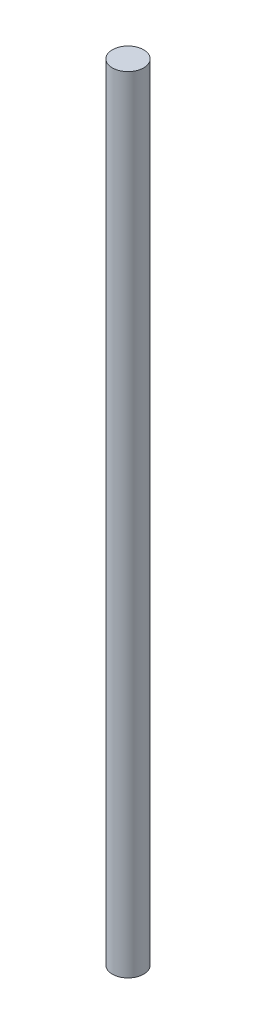
SolidWorks part; units mm, degrees
ref_plane "Plano frontal" through (0, 0, 0) normal (0, 0, 1) x (1, 0, 0)
ref_plane "Plano superior" through (0, 0, 0) normal (0, 1, 0) x (1, 0, 0)
ref_plane "Plano direito" through (0, 0, 0) normal (1, 0, 0) x (0, 0, -1)
sketch "Esboço1" plane through (0, 0, 0) normal (0, 0, 1) x (1, 0, 0)
  line L0 (0, 0) -> (0, 1590) construction
  line L1 (0, 1590) -> (31.75, 1590)
  line L2 (31.75, 1590) -> (31.75, 0)
  line L3 (31.75, 0) -> (0, 0)
  line L4 (0, 0) -> (0, 1590)
  dimension "D1" = 1590
  dimension "D2" = 31.75
revolve "Revolução1" add sketch "Esboço1" angle 360 about L0
